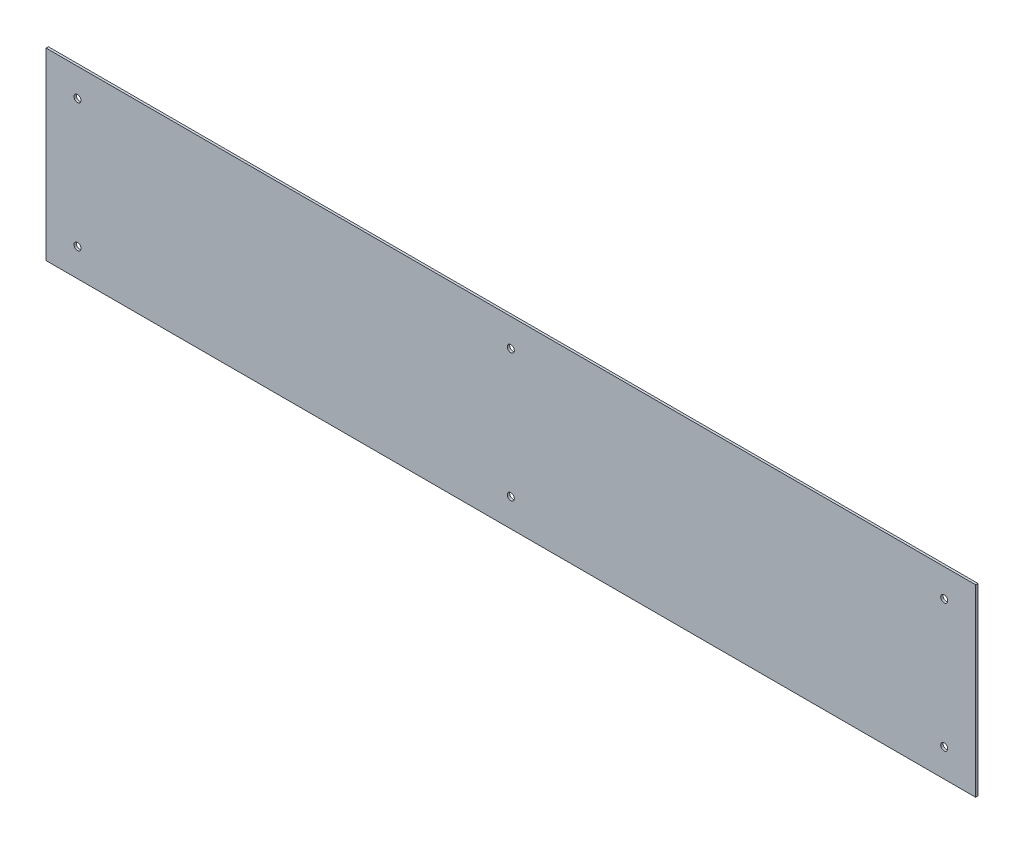
SolidWorks part; units mm, degrees
material "201 Annealed Stainless Steel (SS)"
ref_plane "Front Plane" through (0, 0, 0) normal (0, 0, 1) x (1, 0, 0)
ref_plane "Top Plane" through (0, 0, 0) normal (0, 1, 0) x (1, 0, 0)
ref_plane "Right Plane" through (0, 0, 0) normal (1, 0, 0) x (0, 0, -1)
sketch "Sketch1" plane through (0, 0, 0) normal (0, 0, 1) x (1, 0, 0)
  line L0 (0, 0) -> (0, -146.4794) construction
  line L1 (-399, 79) -> (399, 79)
  line L2 (-399, 79) -> (-399, -79)
  line L3 (-399, -79) -> (399, -79)
  line L4 (399, 79) -> (399, -79)
  line L5 (-399, 79) -> (399, -79) construction
  line L6 (-399, -79) -> (399, 79) construction
  line L7 (0, 0) -> (-417.8368, 0) construction
  circle A0 centre (0, 55) radius 3
  circle A1 centre (-372, 55) radius 3
  circle A2 centre (-372, -55) radius 3
  circle A3 centre (0, -55) radius 3
  circle A4 centre (372, -55) radius 3
  circle A5 centre (372, 55) radius 3
  circle A6 centre (-372, 55) radius 2.5 construction
  point P0 (0, 0)
  dimension "D3" = 6
  dimension "D5" = 21
  dimension "D7" = 24
  dimension "D1" = 158
  dimension "D2" = 798
extrude "Boss-Extrude1" add sketch "Sketch1" along normal mid plane 2
other "DeleteFace1" [suppressed]
sketch "Sketch2" [suppressed] plane through (0, 0, 1) normal (0, 0, 1) x (1, 0, 0)
  line L0 (265.7847, 0) -> (416.352, 0) construction
  line L5 (293.206, -45.5) -> (314.206, -45.5)
  line L6 (293.206, -45.5) -> (293.206, -14.5)
  line L11 (293.206, -14.5) -> (314.206, -14.5)
  line L12 (50.7847, -22.5) -> (95.7847, -22.5)
  line L13 (-93.5, 36.6025) -> (-110.25, 36.6025)
  line L14 (-110.25, 36.6025) -> (-110.25, -45.8975)
  line L15 (-110.25, -45.8975) -> (-49.75, -45.8975)
  line L16 (-49.75, -45.8975) -> (-49.75, 36.6025)
  line L17 (-49.75, 36.6025) -> (-66.5, 36.6025)
  line L18 (-93.5, 36.6025) -> (-110.25, 36.6025)
  line L19 (-110.25, 36.6025) -> (-110.25, -45.8975)
  line L20 (-110.25, -45.8975) -> (-49.75, -45.8975)
  line L21 (-49.75, -45.8975) -> (-49.75, 36.6025)
  line L22 (-49.75, 36.6025) -> (-66.5, 36.6025)
  line L23 (50.7847, 22.5) -> (50.7847, -22.5)
  line L24 (95.7847, 22.5) -> (50.7847, 22.5)
  line L25 (95.7847, -22.5) -> (95.7847, 22.5)
  line L26 (50.7847, -22.5) -> (95.7847, -22.5)
  line L27 (50.7847, 22.5) -> (50.7847, -22.5)
  line L28 (95.7847, 22.5) -> (50.7847, 22.5)
  line L29 (95.7847, -22.5) -> (95.7847, 22.5)
  line L30 (135.7847, -22.5) -> (180.7847, -22.5)
  line L31 (135.7847, 22.5) -> (135.7847, -22.5)
  line L32 (180.7847, 22.5) -> (135.7847, 22.5)
  line L33 (180.7847, -22.5) -> (180.7847, 22.5)
  line L34 (135.7847, -22.5) -> (180.7847, -22.5)
  line L35 (135.7847, 22.5) -> (135.7847, -22.5)
  line L36 (180.7847, 22.5) -> (135.7847, 22.5)
  line L37 (180.7847, -22.5) -> (180.7847, 22.5)
  line L38 (220.7847, -22.5) -> (265.7847, -22.5)
  line L39 (220.7847, 22.5) -> (220.7847, -22.5)
  line L40 (265.7847, 22.5) -> (220.7847, 22.5)
  line L41 (265.7847, -22.5) -> (265.7847, 22.5)
  line L42 (220.7847, -22.5) -> (265.7847, -22.5)
  line L43 (220.7847, 22.5) -> (220.7847, -22.5)
  line L44 (265.7847, 22.5) -> (220.7847, 22.5)
  line L45 (265.7847, -22.5) -> (265.7847, 22.5)
  line L46 (314.206, -45.5) -> (314.206, -14.5)
  line L47 (293.206, -45.5) -> (314.206, -14.5) construction
  line L48 (293.206, -14.5) -> (314.206, -45.5) construction
  line L49 (83.36, 0) -> (-83.36, 0) construction
  line L104 (293.206, -45.5) -> (314.206, -45.5)
  line L105 (293.206, -14.5) -> (293.206, -45.5)
  line L106 (314.206, -14.5) -> (293.206, -14.5)
  line L107 (314.206, -45.5) -> (314.206, -14.5)
  line L108 (293.206, -45.5) -> (314.206, -45.5) construction
  line L109 (293.206, -14.5) -> (293.206, -45.5) construction
  line L110 (314.206, -14.5) -> (293.206, -14.5) construction
  line L111 (314.206, -45.5) -> (314.206, -14.5) construction
  line L165 (-150.5, -45.5) -> (-129.5, -45.5)
  line L166 (-150.5, -14.5) -> (-150.5, -45.5)
  line L167 (-129.5, -14.5) -> (-150.5, -14.5)
  line L168 (-129.5, -45.5) -> (-129.5, -14.5)
  line L169 (-150.5, -45.5) -> (-129.5, -45.5)
  line L170 (-150.5, -14.5) -> (-150.5, -45.5)
  line L171 (-129.5, -14.5) -> (-150.5, -14.5)
  line L172 (-129.5, -45.5) -> (-129.5, -14.5)
  circle A0 centre (303.706, 30) radius 11
  arc A1 (-66.5, 36.6025) -> (-93.5, 36.6025) centre (-80, 35.5625) ccw
  arc A2 (-66.5, 36.6025) -> (-93.5, 36.6025) centre (-80, 35.5625) ccw
  point P25 (303.706, -30)
  dimension "D7" = 22
  dimension "D1" = 0
  dimension "D2" = 0
  dimension "D8" = 30
  dimension "D9" = 30
  dimension "D3" = 0
  dimension "D4" = 0
  dimension "D5" = 0
  dimension "D6" = 0
extrude "Cut-Extrude1" [suppressed] cut sketch "Sketch2" against normal through all
sketch "Sketch3" [suppressed] plane through (0, 0, 1) normal (0, 0, 1) x (1, 0, 0)
  line L0 (0, 0) -> (0, -109.0497) construction
  circle A0 centre (-72, 50) radius 2.5
  circle A1 centre (72, -50) radius 2.5
  circle A2 centre (72, -50) radius 2.5
  circle A3 centre (72, 50) radius 2.5
  circle A4 centre (72, 50) radius 2.5
  circle A5 centre (-72, -50) radius 2.5
  dimension "D1" = 0
  dimension "D2" = 0
extrude "Cut-Extrude2" [suppressed] cut sketch "Sketch3" against normal through all
delete or keep bodies "Body-Delete/Keep 1" [suppressed] type delete bodies bodies 102 103 104 105
other "DeleteFace2" [suppressed]
